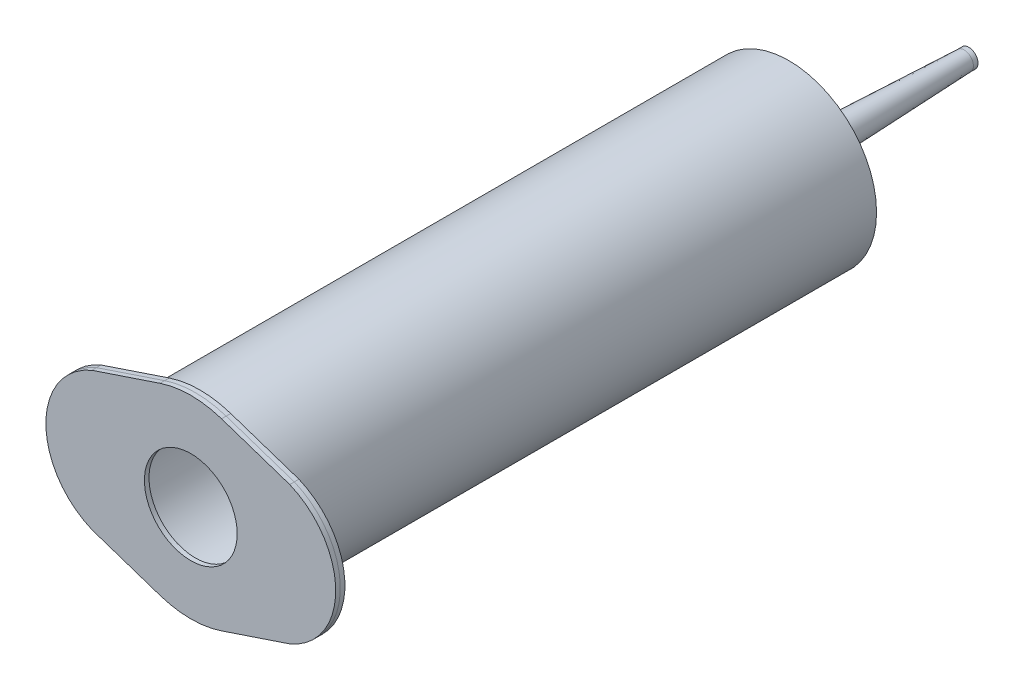
SolidWorks part; units mm, degrees
ref_plane "Front Plane" through (0, 0, 0) normal (0, 0, 1) x (1, 0, 0)
ref_plane "Top Plane" through (0, 0, 0) normal (0, 1, 0) x (1, 0, 0)
ref_plane "Right Plane" through (0, 0, 0) normal (1, 0, 0) x (0, 0, -1)
sketch "Sketch1" plane through (0, 0, 0) normal (0, 0, 1) x (1, 0, 0)
  circle A0 centre (0, 0) radius 15.0813
  circle A1 centre (0, 0) radius 19.05
  dimension "D1" = 30.1625
  dimension "D2" = 3.9688
extrude "Boss-Extrude1" add sketch "Sketch1" along normal blind 127
extrude "Boss-Extrude2" add sketch "Sketch1<2>" against normal blind 2 contours A0 | A1 A0 region at (0, 0, 0) region at (-18.5112, 0, 0)
sketch "Sketch1<2>" plane through (0, 0, 0) normal (0, 0, 1) x (1, 0, 0) same geometry as "Sketch1"
sketch "Sketch2" plane through (0, 0, -2) normal (0, 0, -1) x (-1, 0, 0)
  circle A0 centre (0, 0) radius 2.5
  circle A1 centre (0, 0) radius 3.5
  circle A2 centre (0, 0) radius 1
  circle A3 centre (0, 0) radius 2
  dimension "D1" = 5
  dimension "D2" = 1
  dimension "D3" = 1.5
  dimension "D4" = 1
extrude "Cut-Extrude1" cut sketch "Sketch2" against normal through all contours A0 A3 | A3 A2 | A2 | A2 | A0 region at (2.4293, 0, -2) region at (0, 0, -2) region at (1.9434, 0, -2)
extrude "Boss-Extrude3" add sketch "Sketch2<5>" along normal blind 1 contours A1 A0 region at (3.401, 0, -2)
sketch "Sketch2<5>" plane through (0, 0, -2) normal (0, 0, -1) x (-1, 0, 0) same geometry as "Sketch2"
extrude "Boss-Extrude4" add sketch "Sketch2<6>" along normal blind 1 from offset 38.1 separate body contours A3 A2 region at (1.9434, 0, -2)
sketch "Sketch2<6>" plane through (0, 0, -2) normal (0, 0, -1) x (-1, 0, 0) same geometry as "Sketch2"
sketch "Sketch3" plane through (0, 0, 0) normal (1, 0, 0) x (0, 0, -1)
  line L0 (3, 3.5) -> (40.1, 2)
  line L1 (40.1, 2) -> (40.1, 1)
  line L3 (3, 2.5) -> (40.1, 1)
  line L4 (3, 3.5) -> (3, 2.5)
  dimension "D1" = 1
ref_axis "Axis1" through (0, 0, 158.4) along (0, 0, -1)
revolve "Revolve1" add sketch "Sketch3" angle 360 about axis through (0, 0, 158.4) along (0, 0, -1)
sketch "Sketch4" plane through (0, 0, 127) normal (0, 0, 1) x (1, 0, 0)
  line L0 (31.5, 0) -> (-31.5, 0) construction
  line L1 (-21.5, 15) -> (-21.5, -15) construction
  line L2 (-21.5, 15) -> (-6.6832, 19.9609)
  line L3 (-21.5, -15) -> (-6.6832, -19.9609)
  line L4 (0, -1000) -> (0, 49000) construction
  line L5 (21.5, -15) -> (6.6832, -19.9609)
  line L6 (21.5, 15) -> (6.6832, 19.9609)
  circle A0 centre (0, 0) radius 15.0813 construction
  circle A1 centre (0, 0) radius 15.0813
  circle A2 centre (0, 0) radius 10.0813
  arc A3 (-21.5, 15) -> (-21.5, -15) centre (-15.25, 0) ccw
  arc A4 (21.5, 15) -> (21.5, -15) centre (15.25, 0) cw
  circle A5 centre (0, 0) radius 21.05
  arc A6 (-6.6832, -19.9609) -> (6.6832, -19.9609) centre (0, 0) ccw
  arc A7 (6.6832, 19.9609) -> (-6.6832, 19.9609) centre (0, 0) ccw
  point P8 (0, 0)
  point P13 (-21.5, 0)
  circle M3 centre (0, 0) radius 19.05
  circle M4 centre (0, 0) radius 15.0813
  dimension "D3" = 63
  dimension "D4" = 30
  dimension "D5" = 10
  dimension "D1" = 5
  dimension "D2" = 2
extrude "Boss-Extrude5" add sketch "Sketch4" against normal blind 1 separate body contours L6 A7 L2 A3 L3 A6 L5 A4 M3 region at (-23.3782, 0, 127) region at (0, 20.4546, 127) region at (23.3782, 0, 127)
extrude "Boss-Extrude6" add sketch "Sketch4<3>" along normal blind 1 contours L6 A7 L2 A3 L3 A6 L5 A4 M3 | M3 M4 | A2 M4 region at (-23.3782, 0, 127) region at (0, 20.4546, 127) region at (23.3782, 0, 127) region at (-14.6547, 0, 127) region at (-18.5112, 0, 127)
sketch "Sketch4<3>" plane through (0, 0, 127) normal (0, 0, 1) x (1, 0, 0) same geometry as "Sketch4"
